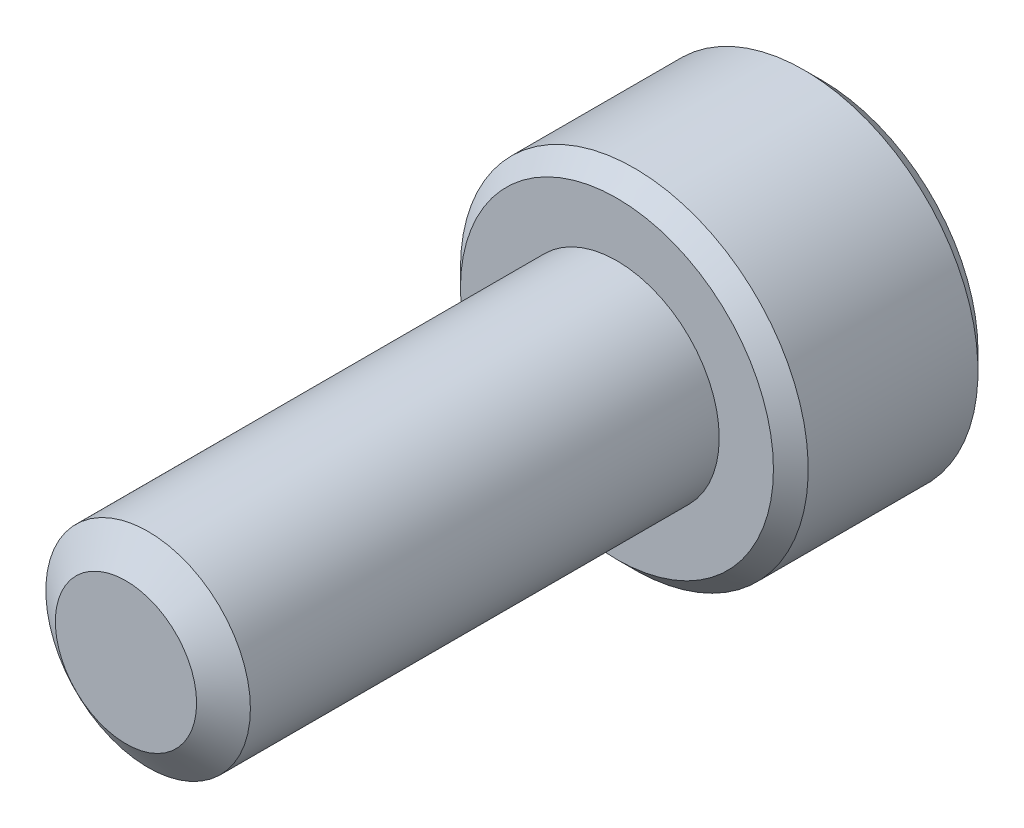
SolidWorks part; units mm, degrees
other "DetailItem1"
material "1.4310 (X10CrNi18-8)"
ref_plane "Front Plane" through (0, 0, 0) normal (0, 0, 1) x (1, 0, 0)
ref_plane "Top Plane" through (0, 0, 0) normal (0, 1, 0) x (1, 0, 0)
ref_plane "Right Plane" through (0, 0, 0) normal (1, 0, 0) x (0, 0, -1)
sketch "Sketch1" plane through (0, 0, 0) normal (0, 0, 1) x (1, 0, 0)
  circle A0 centre (0, 0) radius 2.5
  dimension "OD" = 5
extrude "Extrude1" add sketch "Sketch1" against normal blind 12
sketch "Sketch2" plane through (0, 0, 0) normal (0, 0, 1) x (1, 0, 0)
  circle A0 centre (0, 0) radius 2.5 construction
  circle A1 centre (0, 0) radius 2.5
curve "Helix/Spiral1" pitch 0.8 height 12.8 turns 16 parameters "pitch"=0.8
sketch "Sketch3" plane through (0, 0, 0) normal (1, 0, 0) x (0, 0, -1)
  line L0 (-0.7, 2.5) -> (-0.4, 1.9804)
  line L1 (-0.4, 1.9804) -> (-0.3, 1.9804)
  line L2 (-0.3, 1.9804) -> (0, 2.5)
  line L3 (-0.7, 2.5) -> (0, 2.5)
  line L4 (-0.35, 2.5) -> (-0.35, 1.9804) construction
  line L5 (-0.55, 2.2402) -> (-0.15, 2.2402) construction
  line L6 (0, 2.5) -> (0, -2.5) construction
  dimension "D1" = 0.1
  dimension "D2" = 0.4
  dimension "D3" = 60
sweep "Cut-Sweep1" [suppressed] cut profiles "Sketch3" path "Helix/Spiral1"
sketch "Sketch4" plane through (0, 0, 0) normal (1, 0, 0) x (0, 0, -1)
  line L0 (0.5417, 2.5) -> (0, 1.7264)
  line L1 (0, 1.7264) -> (0, 2.5)
  line L2 (0.5417, 2.5) -> (0, 2.5)
  line L3 (-0.7, 2.5) -> (0, 2.5) construction
  line L4 (0, 0) -> (7.0209, 0) construction
  dimension "D1" = 55
  dimension "D2" = 0.254
revolve "Cut-Revolve1" cut sketch "Sketch4" angle 360 about L4
sketch "Sketch6" plane through (0, 0, -12) normal (0, 0, -1) x (-1, 0, 0)
  circle A0 centre (0, 0) radius 4.25
  dimension "head dia" = 8.5
extrude "Extrude2" add sketch "Sketch6" along normal blind 5
sketch "Sketch7" plane through (0, 0, -17) normal (0, 0, -1) x (-1, 0, 0)
  line L1 (0, 2.3094) -> (-2, 1.1547)
  line L2 (-2, 1.1547) -> (-2, -1.1547)
  line L3 (-2, -1.1547) -> (0, -2.3094)
  line L4 (0, -2.3094) -> (2, -1.1547)
  line L5 (2, -1.1547) -> (2, 1.1547)
  line L6 (2, 1.1547) -> (0, 2.3094)
  circle A0 centre (0, 0) radius 2 construction
  dimension "hex dia" = 4
extrude "Cut-Extrude1" cut sketch "Sketch7" against normal blind 3
sketch "Sketch8" plane through (0, 0, -17) normal (0, 0, -1) x (-1, 0, 0)
  circle A0 centre (0, 0) radius 2.3094
extrude "Cut-Extrude2" cut sketch "Sketch8" against normal through all draft 45
chamfer "Chamfer1" distance 0.425 angle 45 2 edges at (-4.25, 0, -17) (-4.25, 0, -12)
sketch "Sketch10" plane through (0, 0, -12) normal (0, 0, 1) x (1, 0, 0)
  circle A1 centre (0, 0) radius 2.5
  circle A2 centre (0, 0) radius 2.5
  dimension "D1" = 0
ref_plane "Plane1" through (0, 0, 0) normal (0, 0, 1) x (1, 0, 0)
extrude "partial thread" [suppressed] add sketch "Sketch10" along normal up to surface (13 mm away) separate body up to plane "Plane1"
chamfer "Chamfer2" [suppressed] distance 0.1 angle 45
combine bodies "Combine1" [suppressed] operation type add bodies to combine 107 108
sketch "Sketch9" plane through (0, 0, 0) normal (1, 0, 0) x (0, 0, -1)
  line L0 (0, 2.5) -> (0, -2.5) construction
  line L1 (2, 2.5) -> (2, -2.5) construction
  dimension "D1" = 2
equation "\"D3@Helix/Spiral1\" = \"screw length@Extrude1\"+\"pitch@Helix/Spiral1\""
equation "\"D1@Sketch3\" = \"pitch@Helix/Spiral1\"*.125"
equation "\"D2@Sketch3\" = \"pitch@Helix/Spiral1\"*.5"
equation "\"D1@Cut-Extrude1\" = \"hex dia@Sketch7\"*.75"
equation "\"D1@Chamfer1\" = \"head dia@Sketch6\"*.05"
equation "\"D1@Sketch9\" = \"pitch@Helix/Spiral1\"*2.5"
equation "\"D1@Chamfer2\"=\"OD@Sketch1\"*.02"
